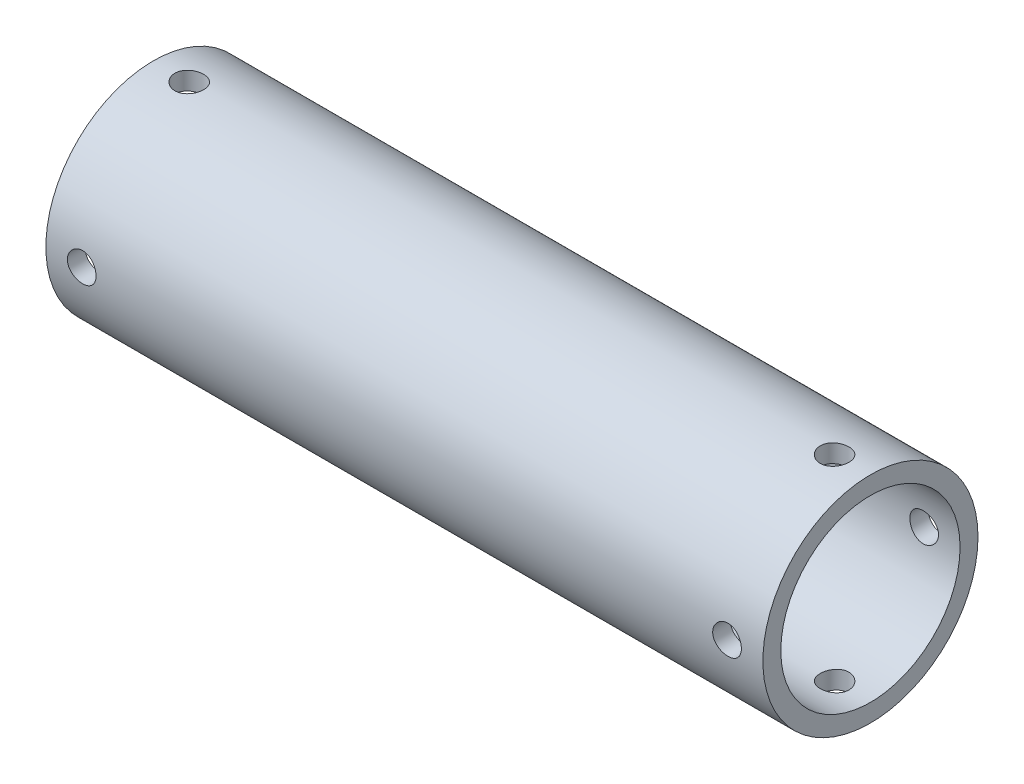
SolidWorks part; units mm, degrees
material "1060-H16"
ref_plane "Спереди" through (0, 0, 0) normal (0, 0, 1) x (1, 0, 0)
ref_plane "Сверху" through (0, 0, 0) normal (0, 1, 0) x (1, 0, 0)
ref_plane "Справа" through (0, 0, 0) normal (1, 0, 0) x (0, 0, -1)
other "Configuration Table"
sketch "Эскиз2" plane through (0, 0, 0) normal (1, 0, 0) x (0, 0, -1)
  circle A0 centre (0, 0) radius 30
  circle A1 centre (0, 0) radius 25
  dimension "D1" = 60
  dimension "D2" = 50
extrude "Бобышка-Вытянуть2" add sketch "Эскиз2" along normal blind 200
ref_plane "Плоскость1" through (0, 0, 25) normal (0, 0, 1) x (1, 0, 0)
sketch "Эскиз4" plane through (0, 0, 25) normal (0, 0, 1) x (1, 0, 0)
  line L0 (0, -30) -> (200, -30) construction
  line L1 (200, -30) -> (200, 30) construction
  circle A0 centre (10, 0) radius 4
  circle A1 centre (190, 0) radius 4
  point P6 (0, 0)
  dimension "D1" = 8
  dimension "D4" = 8
  dimension "D2" = 10
  dimension "D3" = 30
  dimension "D5" = 10
extrude "Вырез-Вытянуть2" cut sketch "Эскиз4" against normal blind 10 and the other way blind 10 contours A0 | A1
pattern_circular "Круговой массив1" count 4 over 360 about axis through (200, 0, 0) along (-1, 0, 0) of "Вырез-Вытянуть2"
equation "\"Diameter\"= 60мм"
equation "\"D1@Эскиз2\"= \"Diameter\""
equation "\"Length\"= 200мм"
equation "\"Thickness\"= 5мм"
equation "\"D1@Бобышка-Вытянуть2\"= \"Length\""
equation "\"D2@Эскиз2\" = \"Diameter\" - \"Thickness\" * 2"
equation "\"D4@Эскиз4\"=\"D1@Эскиз4\""
equation "\"D5@Эскиз4\"=\"D2@Эскиз4\""
equation "\"D3@Эскиз4\"=\"Diameter\"/2"
